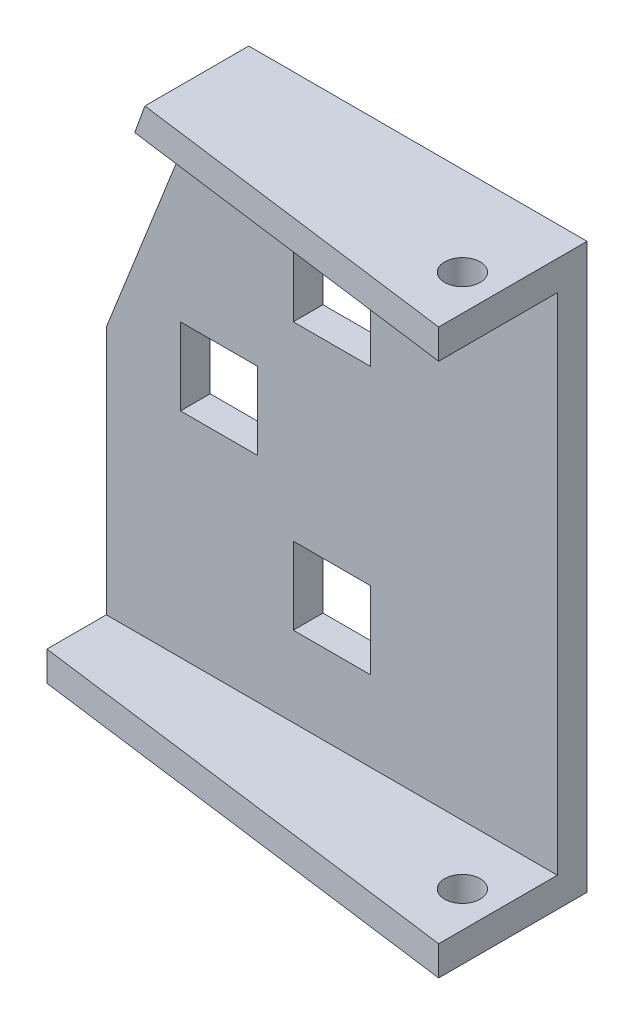
SolidWorks part; units mm, degrees
ref_plane "Front Plane" through (0, 0, 0) normal (0, 0, 1) x (1, 0, 0)
ref_plane "Top Plane" through (0, 0, 0) normal (0, 1, 0) x (1, 0, 0)
ref_plane "Right Plane" through (0, 0, 0) normal (1, 0, 0) x (0, 0, -1)
sketch "Sketch1" plane through (0, 0, 0) normal (0, 0, 1) x (1, 0, 0)
  line L0 (-70, 0) -> (6, 0)
  line L1 (6, 0) -> (6, 95)
  line L2 (6, 95) -> (-51, 95)
  line L3 (-51, 95) -> (-70, 47)
  line L4 (-70, 47) -> (-70, 0)
  dimension "D1" = 76
  dimension "D2" = 70
  dimension "D3" = 57
  dimension "D4" = 48
  dimension "D5" = 95
extrude "Boss-Extrude1" add sketch "Sketch1" along normal blind 5
sketch "Sketch2" plane through (0, 0, 5) normal (0, 0, 1) x (1, 0, 0)
  line L0 (6, 95) -> (-51, 95) construction
  line L1 (-38.5, 76.5) -> (-25.5, 76.5)
  line L2 (-38.5, 76.5) -> (-38.5, 63.5)
  line L3 (-38.5, 63.5) -> (-25.5, 63.5)
  line L4 (-25.5, 76.5) -> (-25.5, 63.5)
  line L5 (-38.5, 31.5) -> (-25.5, 31.5)
  line L6 (-38.5, 31.5) -> (-38.5, 18.5)
  line L7 (-38.5, 18.5) -> (-25.5, 18.5)
  line L8 (-25.5, 31.5) -> (-25.5, 18.5)
  line L9 (-57.5, 54) -> (-44.5, 54)
  line L10 (-57.5, 54) -> (-57.5, 41)
  line L11 (-57.5, 41) -> (-44.5, 41)
  line L12 (-44.5, 54) -> (-44.5, 41)
  line L13 (-70, 47) -> (-70, 0) construction
  point P12 (-25.5, 70)
  point P15 (-25.5, 25)
  point P16 (-44.5, 47.5)
  point P19 (-51, 41)
  point P20 (-32, 18.5)
  dimension "D1" = 25
  dimension "D2" = 70
  dimension "D3" = 47.5
  dimension "D4" = 19
  dimension "D5" = 38
  dimension "D6" = 13
extrude "Cut-Extrude1" cut sketch "Sketch2" against normal through all
sketch "Sketch5" plane through (0, 0, 5) normal (0, 0, 1) x (1, 0, 0)
  line L0 (-51, 95) -> (-52.9792, 90)
  line L1 (-51, 95) -> (-70, 47) construction
  line L2 (-52.9792, 90) -> (6, 90)
  line L3 (6, 0) -> (6, 95) construction
  line L4 (6, 90) -> (6, 95)
  line L5 (6, 95) -> (-51, 95)
  line L6 (-70, 0) -> (6, 0)
  line L7 (6, 0) -> (6, 5)
  line L8 (6, 5) -> (-70, 5)
  line L9 (-70, 47) -> (-70, 0) construction
  line L10 (-70, 5) -> (-70, 0)
  dimension "D1" = 5
  dimension "D2" = 5
extrude "Boss-Extrude3" add sketch "Sketch5" along normal blind 20
sketch "Sketch6" plane through (0, 0, 0) normal (0, -1, 0) x (1, 0, 0)
  line L1 (6, 25) -> (-70, 15)
  line L2 (-70, 25) -> (-70, 0) construction
  line L5 (-70, 15) -> (-70, 25)
  line L6 (-70, 25) -> (6, 25)
  line L7 (-70, 0) -> (6, 0) construction
  dimension "D1" = 15
extrude "Cut-Extrude2" cut sketch "Sketch6" against normal through all
sketch "Sketch7" plane through (0, 95, 0) normal (0, 1, 0) x (1, 0, 0)
  line L6 (6, -5) -> (-70, -5) construction
  line L7 (6, -25) -> (6, -5) construction
  circle A0 centre (0, -15) radius 3
  dimension "D1" = 6
  dimension "D2" = 10
  dimension "D3" = 6
extrude "Cut-Extrude4" cut sketch "Sketch7" against normal through all
